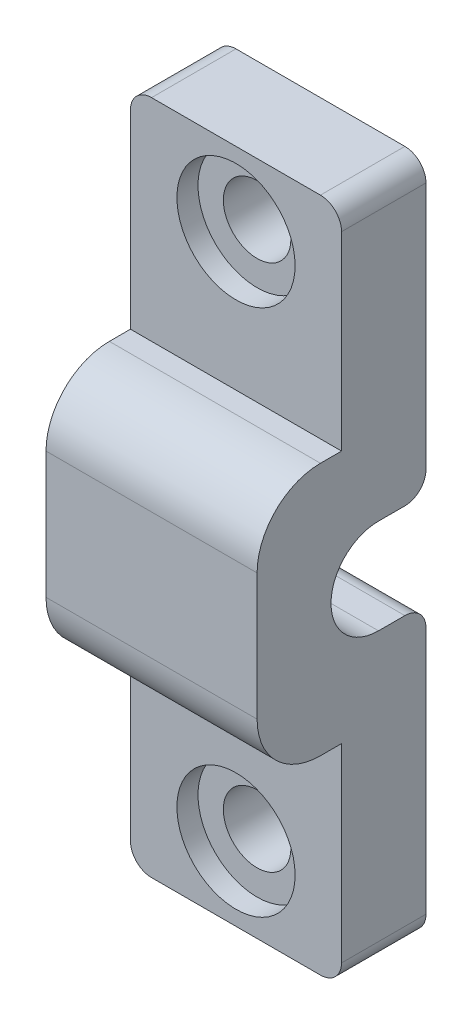
SolidWorks part; units mm, degrees
ref_plane "Alzado" through (0, 0, 0) normal (0, 0, 1) x (1, 0, 0)
ref_plane "Planta" through (0, 0, 0) normal (0, 1, 0) x (1, 0, 0)
ref_plane "Vista lateral" through (0, 0, 0) normal (1, 0, 0) x (0, 0, -1)
sketch "Croquis1" plane through (0, 0, 0) normal (0, 0, 1) x (1, 0, 0)
  line L1 (0, 0) -> (10, 0)
  line L2 (0, 0) -> (0, 32)
  line L3 (0, 32) -> (10, 32)
  line L4 (10, 0) -> (10, 32)
  dimension "D1" = 10
  dimension "D2" = 32
extrude "Saliente-Extruir1" add sketch "Croquis1" along normal blind 8
sketch "Croquis2" plane through (0, 0, 8) normal (0, 0, 1) x (1, 0, 0)
  line L0 (5, 32) -> (5, 0) construction
  line L1 (10, 32) -> (0, 32) construction
  line L2 (0, 0) -> (10, 0) construction
  circle A0 centre (5, 28.5) radius 1.6
  circle A1 centre (5, 3.5) radius 1.6
  dimension "D1" = 3.2
  dimension "D2" = 3.2
  dimension "D3" = 25
  dimension "D4" = 3.5
extrude "Cortar-Extruir1" cut sketch "Croquis2" against normal up to surface (8 mm away) up to face at (5, 16, 0)
sketch "Croquis3" plane through (0, 0, 0) normal (-1, 0, 0) x (0, 0, 1)
  line L6 (0, 32) -> (0, 0) construction
  line L7 (8, 32) -> (0, 32) construction
  line L8 (2.25, 18.25) -> (0, 18.25)
  line L9 (2.25, 13.75) -> (0, 13.75)
  line L10 (0, 13.75) -> (0, 18.25)
  circle A0 centre (2.25, 16) radius 2.25
  line M2 (0, 32) -> (0, 0)
  dimension "D2" = 4.5
  dimension "D1" = 16
extrude "Cortar-Extruir2" cut sketch "Croquis3" against normal up to surface (10 mm away) contours A0 | A0 L8 M2 | A0 L10 L9 region at (0, 17.7474, 0.5026) region at (0, 16, 2.25) region at (0, 14.2526, 0.5026) up to face at (10, 16, 4)
fillet "Redondeo1" radius 1 2 edges at (5, 13.75, 0) (5, 18.25, 0)
sketch "Croquis4" plane through (0, 0, 0) normal (-1, 0, 0) x (0, 0, 1)
  line L1 (8, 32) -> (4, 32)
  line L2 (8, 32) -> (8, 22)
  line L3 (8, 22) -> (4, 22)
  line L4 (4, 32) -> (4, 22)
  line L5 (8, 0) -> (4, 0)
  line L6 (8, 0) -> (8, 10)
  line L7 (8, 10) -> (4, 10)
  line L8 (4, 0) -> (4, 10)
  dimension "D1" = 4
  dimension "D2" = 4
  dimension "D3" = 10
  dimension "D4" = 10
extrude "Cortar-Extruir3" cut sketch "Croquis4" against normal up to surface (10 mm away) up to face at (10, 16, 2.4336)
fillet "Redondeo2" radius 3 2 edges at (5, 10, 8) (5, 22, 8)
fillet "Redondeo3" radius 1 4 edges at (10, 32, 2) (0, 32, 2) (0, 0, 2) (10, 0, 2)
sketch "Croquis5" plane through (0, 0, 4) normal (0, 0, 1) x (1, 0, 0)
  circle A0 centre (5, 28.5) radius 2.8
  circle A1 centre (5, 3.5) radius 2.8
  dimension "D1" = 5.6
extrude "Cortar-Extruir4" cut sketch "Croquis5" against normal blind 1
